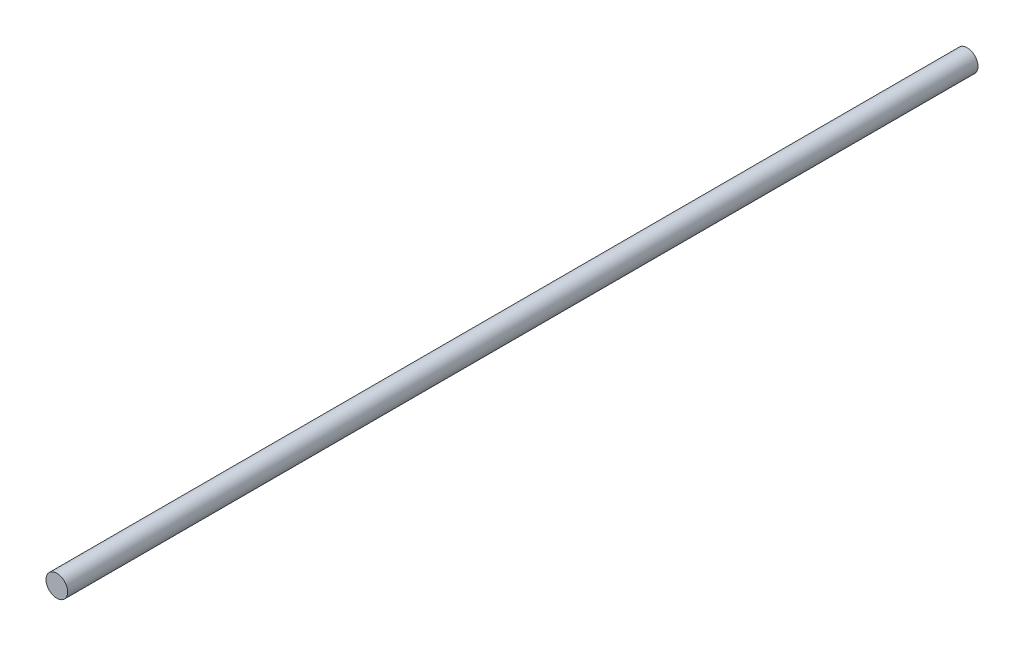
SolidWorks part; units mm, degrees
material "AISI 316 Stainless Steel Sheet (SS)"
ref_plane "Front (1)" through (0, 0, 0) normal (0, 0, 1) x (1, 0, 0)
ref_plane "Top (2)" through (0, 0, 0) normal (0, 1, 0) x (1, 0, 0)
ref_plane "Right (3)" through (0, 0, 0) normal (1, 0, 0) x (0, 0, -1)
ref_axis "X Axis" through (13.5064, 0, 0) along (-1, 0, 0)
ref_axis "Y Axis" through (0, 12.3593, 0) along (0, -1, 0)
ref_axis "Z Axis" through (0, 0, 14.1119) along (0, 0, -1)
sketch "Sketch2" plane through (0, 0, 0) normal (1, 0, 0) x (0, 0, -1)
  line L0 (-7.8, 0) -> (0, 0) construction
  line L1 (-7.8, 0) -> (327.8277, 0)
  line L2 (-7.8, 0) -> (-7.8, 4)
  line L3 (-7.8, 4) -> (327.8277, 4)
  line L4 (327.8277, 0) -> (327.8277, 4)
  dimension "D1" = 335.6277
  dimension "D2" = 4
revolve "Revolve1" add sketch "Sketch2" angle 360 about L0
